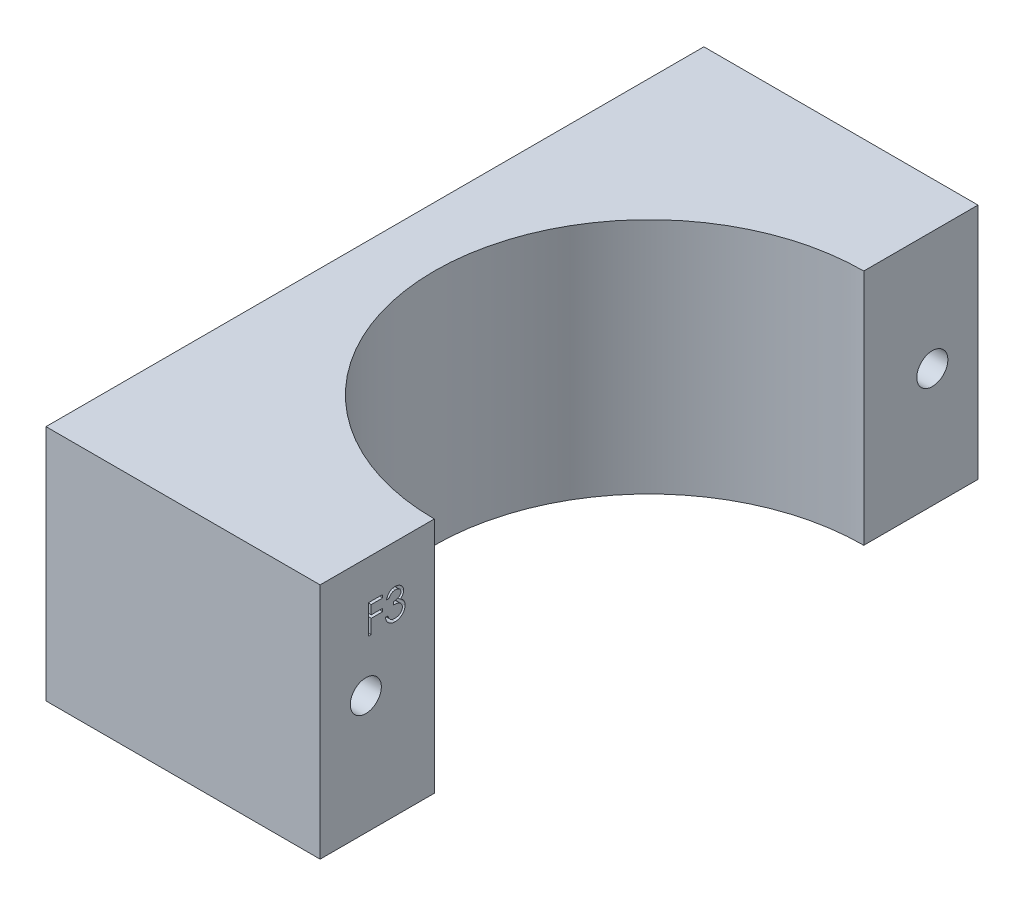
SolidWorks part; units mm, degrees
ref_plane "Front Plane" through (0, 0, 0) normal (0, 0, 1) x (1, 0, 0)
ref_plane "Top Plane" through (0, 0, 0) normal (0, 1, 0) x (1, 0, 0)
ref_plane "Right Plane" through (0, 0, 0) normal (1, 0, 0) x (0, 0, -1)
sketch "Sketch1" plane through (0, 0, 0) normal (0, 1, 0) x (1, 0, 0)
  line L0 (-46.9983, 32.5286) -> (-46.9983, -39.4714)
  line L1 (-46.9983, -39.4714) -> (-16.9983, -39.4714)
  line L2 (-16.9983, -39.4714) -> (-16.9983, -26.9714)
  line L3 (-46.9983, 32.5286) -> (-16.9983, 32.5286)
  line L4 (-16.9983, 32.5286) -> (-16.9983, 20.0286)
  arc A0 (-16.9983, 20.0286) -> (-16.9983, -26.9714) centre (-16.9983, -3.4714) ccw
  dimension "D1" = 72
  dimension "D2" = 30
  dimension "D3" = 30
  dimension "D4" = 12.5
  dimension "D5" = 12.5
extrude "Boss-Extrude1" add sketch "Sketch1" along normal blind 26
sketch "Sketch2" plane through (-16.9983, 0, 0) normal (1, 0, 0) x (0, 0, -1)
  line L0 (-34.4714, 26) -> (-34.4714, 0) construction
  line L1 (-39.4714, 26) -> (-26.9714, 26) construction
  line L2 (-39.4714, 0) -> (-26.9714, 0) construction
  line L3 (27.5286, 26) -> (27.5286, 0) construction
  line L4 (20.0286, 26) -> (32.5286, 26) construction
  line L5 (20.0286, 0) -> (32.5286, 0) construction
  line L6 (-39.4714, 26) -> (-39.4714, 0) construction
  line L7 (32.5286, 26) -> (32.5286, 0) construction
  circle A0 centre (-34.4714, 13) radius 1.7
  circle A1 centre (27.5286, 13) radius 1.7
  dimension "D1" = 5
  dimension "D2" = 5
extrude "Cut-Extrude1" cut sketch "Sketch2" against normal through all
sketch "Sketch3" plane through (-16.9983, 0, 0) normal (1, 0, 0) x (0, 0, -1)
  text T0 "F3"
extrude "Cut-Extrude2" cut sketch "Sketch3" against normal blind 1
